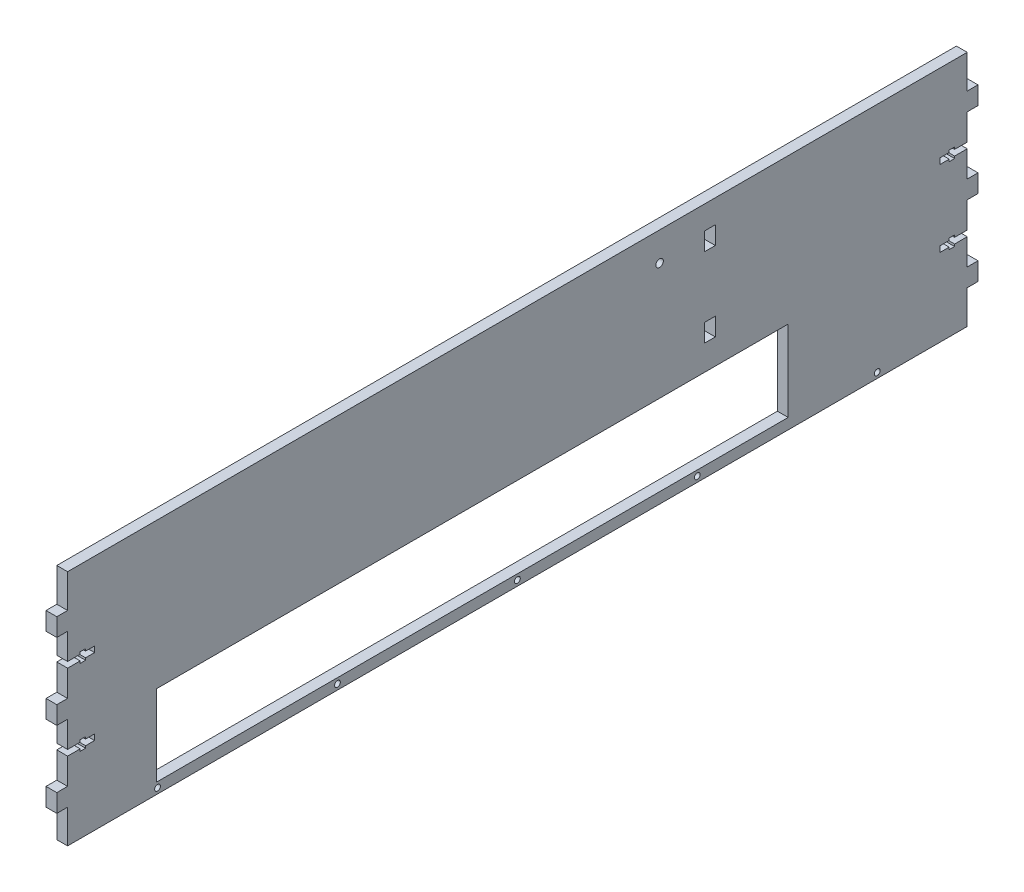
SolidWorks part; units mm, degrees
ref_plane "Front Plane" through (0, 0, 0) normal (0, 0, 1) x (1, 0, 0)
ref_plane "Top Plane" through (0, 0, 0) normal (0, 1, 0) x (1, 0, 0)
ref_plane "Right Plane" through (0, 0, 0) normal (1, 0, 0) x (0, 0, -1)
sketch "Sketch1" plane through (0, 0, 0) normal (1, 0, 0) x (0, 0, -1)
  line L1 (-250, -66) -> (250, -66)
  line L2 (-250, -66) -> (-250, 66)
  line L3 (-250, 66) -> (250, 66)
  line L4 (250, -66) -> (250, 66)
  line L5 (-250, -66) -> (250, 66) construction
  line L6 (-250, 66) -> (250, -66) construction
  point P0 (0, 0)
  dimension "D1" = 132
  dimension "D2" = 500
extrude "Boss-Extrude1" add sketch "Sketch1" along normal blind 6
sketch "Sketch4" plane through (0, 0, 250) normal (0, 0, 1) x (1, 0, 0)
  line L0 (0, 66) -> (0, -66) construction
  line L1 (0, 47.3321) -> (6, 47.3321)
  line L2 (0, 47.3321) -> (0, 37.3321)
  line L3 (0, 37.3321) -> (6, 37.3321)
  line L4 (6, 47.3321) -> (6, 37.3321)
  line L5 (6, 66) -> (6, -66) construction
  line L6 (0, 37.3321) -> (6, 37.3321) construction
  line L7 (0, -66) -> (0, 66) construction
  line L8 (6, 47.3321) -> (0, 47.3321) construction
  line L9 (0, -5) -> (6, -5) construction
  line L10 (0, -5) -> (6, -5)
  line L11 (0, -5) -> (0, 5)
  line L12 (0, 5) -> (6, 5)
  line L13 (6, -5) -> (6, 5)
  line L14 (6, -66) -> (6, 66) construction
  line L15 (6, 5) -> (0, 5) construction
  line L16 (6, -37.3321) -> (0, -37.3321) construction
  line L17 (0, -47.3321) -> (6, -47.3321)
  line L18 (0, -47.3321) -> (0, -37.3321)
  line L19 (0, -37.3321) -> (6, -37.3321)
  line L20 (6, -47.3321) -> (6, -37.3321)
  line L21 (0, -47.3321) -> (6, -47.3321) construction
extrude "Boss-Extrude2" add sketch "Sketch4" along normal blind 6
sketch "Sketch5" plane through (0, 0, 0) normal (-1, 0, 0) x (0, 0, 1)
  line L0 (250, 37.3321) -> (250, 5) construction
  line L1 (250, 5) -> (250, -5) construction
  line L2 (250, -5) -> (250, -37.3321) construction
  line L3 (250, 21.1661) -> (235, 21.1661) construction
  line L4 (240, -23.9661) -> (243, -18.3661) construction
  line L5 (250, 22.7661) -> (235, 22.7661)
  line L6 (240, -18.3661) -> (243, -23.9661) construction
  line L7 (250, 19.5661) -> (235, 19.5661)
  line L8 (250, -21.1661) -> (235, -21.1661) construction
  line L9 (250, 22.7661) -> (250, 19.5661)
  line L10 (235, 22.7661) -> (235, 19.5661)
  line L11 (243, -18.3661) -> (243, -23.9661)
  line L12 (240, -23.9661) -> (243, -23.9661)
  line L13 (250, 0) -> (222.8268, 0) construction
  line L14 (240, 18.3661) -> (243, 18.3661)
  line L15 (240, 18.3661) -> (240, 23.9661)
  line L16 (240, 23.9661) -> (243, 23.9661)
  line L17 (243, 18.3661) -> (243, 23.9661)
  line L18 (240, 18.3661) -> (243, 23.9661) construction
  line L19 (240, 23.9661) -> (243, 18.3661) construction
  line L20 (240, -18.3661) -> (240, -23.9661)
  line L21 (240, -18.3661) -> (243, -18.3661)
  line L22 (235, -22.7661) -> (235, -19.5661)
  line L23 (250, -22.7661) -> (250, -19.5661)
  line L24 (250, -19.5661) -> (235, -19.5661)
  line L25 (250, -22.7661) -> (235, -22.7661)
  point P20 (241.5, 21.1661)
  point P29 (241.5, -21.1661)
  dimension "D3" = 15
  dimension "D4" = 7
  dimension "D5" = 3
  dimension "D6" = 5.6
  dimension "D1" = 1.6
  dimension "D2" = 1.6
extrude "Cut-Extrude3" cut sketch "Sketch5" against normal up to next contours L17 L7 L9 L5 | L7 L17 L5 L15 | L5 L17 L16 L15 | L14 L17 L7 L15 | L7 L15 L5 L10 | L25 L23 L24 L11 | L25 L11 L24 L20 | L24 L11 L21 L20 | L11 L25 L20 L12 | L25 L20 L24 L22 region at (0, 21.1661, 246.5) region at (0, 21.1661, 241.5) region at (0, 23.3661, 241.5) region at (0, 21.1661, 237.5) region at (0, 18.9661, 241.5) region at (0, -18.9661, 241.5) region at (0, -21.1661, 246.5) region at (0, -21.1661, 241.5) region at (0, -23.3661, 241.5) region at (0, -21.1661, 237.5)
sketch "Sketch6" plane through (0, 0, -250) normal (0, 0, -1) x (-1, 0, 0)
  line L0 (0, 47.3321) -> (0, 37.3321) construction
  line L1 (0, 37.3321) -> (-6, 37.3321) construction
  line L2 (-6, 37.3321) -> (-6, 47.3321) construction
  line L3 (-6, 47.3321) -> (0, 47.3321) construction
  line L4 (0, 5) -> (0, -5) construction
  line L5 (0, -5) -> (-6, -5) construction
  line L6 (-6, -5) -> (-6, 5) construction
  line L7 (-6, 5) -> (0, 5) construction
  line L8 (0, -37.3321) -> (0, -47.3321) construction
  line L9 (0, -47.3321) -> (-6, -47.3321) construction
  line L10 (-6, -47.3321) -> (-6, -37.3321) construction
  line L11 (-6, -37.3321) -> (0, -37.3321) construction
  line L12 (0, 47.3321) -> (0, 37.3321)
  line L13 (0, 37.3321) -> (-6, 37.3321)
  line L14 (-6, 37.3321) -> (-6, 47.3321)
  line L15 (-6, 47.3321) -> (0, 47.3321)
  line L16 (0, 5) -> (0, -5)
  line L17 (0, -5) -> (-6, -5)
  line L18 (-6, -5) -> (-6, 5)
  line L19 (-6, 5) -> (0, 5)
  line L20 (0, -37.3321) -> (0, -47.3321)
  line L21 (0, -47.3321) -> (-6, -47.3321)
  line L22 (-6, -47.3321) -> (-6, -37.3321)
  line L23 (-6, -37.3321) -> (0, -37.3321)
extrude "Boss-Extrude3" add sketch "Sketch6" along normal blind 6
sketch "Sketch7" plane through (0, 0, 0) normal (-1, 0, 0) x (0, 0, 1)
  line L0 (0, 0) -> (0, -63.2146) construction
  line L1 (240, 22.7661) -> (240, 23.9661) construction
  line L2 (240, 22.7661) -> (235, 22.7661) construction
  line L3 (235, 22.7661) -> (235, 19.5661) construction
  line L4 (240, 19.5661) -> (235, 19.5661) construction
  line L5 (240, 18.3661) -> (240, 19.5661) construction
  line L6 (240, 18.3661) -> (243, 18.3661) construction
  line L7 (243, 18.3661) -> (243, 19.5661) construction
  line L8 (250, 19.5661) -> (243, 19.5661) construction
  line L9 (250, 22.7661) -> (243, 22.7661) construction
  line L10 (240, 23.9661) -> (243, 23.9661) construction
  line L11 (243, 22.7661) -> (243, 23.9661) construction
  line L12 (240, 22.7661) -> (235, 22.7661) construction
  line L13 (235, 22.7661) -> (235, 19.5661) construction
  line L14 (240, 19.5661) -> (235, 19.5661) construction
  line L15 (240, 18.3661) -> (240, 19.5661) construction
  line L16 (240, 18.3661) -> (243, 18.3661) construction
  line L17 (243, 18.3661) -> (243, 19.5661) construction
  line L18 (250, 19.5661) -> (243, 19.5661) construction
  line L19 (250, 22.7661) -> (243, 22.7661) construction
  line L20 (240, 23.9661) -> (243, 23.9661) construction
  line L21 (243, 22.7661) -> (243, 23.9661) construction
  line L22 (240, 22.7661) -> (240, 23.9661) construction
  line L23 (250, -19.5661) -> (243, -19.5661) construction
  line L24 (240, -18.3661) -> (243, -18.3661) construction
  line L25 (243, -18.3661) -> (243, -19.5661) construction
  line L26 (240, -18.3661) -> (240, -19.5661) construction
  line L27 (240, -19.5661) -> (235, -19.5661) construction
  line L28 (235, -22.7661) -> (235, -19.5661) construction
  line L29 (240, -22.7661) -> (235, -22.7661) construction
  line L30 (240, -22.7661) -> (240, -23.9661) construction
  line L31 (240, -23.9661) -> (243, -23.9661) construction
  line L32 (243, -22.7661) -> (243, -23.9661) construction
  line L33 (250, -22.7661) -> (243, -22.7661) construction
  line L34 (250, -19.5661) -> (243, -19.5661) construction
  line L35 (240, -18.3661) -> (243, -18.3661) construction
  line L36 (243, -18.3661) -> (243, -19.5661) construction
  line L37 (240, -18.3661) -> (240, -19.5661) construction
  line L38 (240, -19.5661) -> (235, -19.5661) construction
  line L39 (235, -22.7661) -> (235, -19.5661) construction
  line L40 (240, -22.7661) -> (235, -22.7661) construction
  line L41 (240, -22.7661) -> (240, -23.9661) construction
  line L42 (240, -23.9661) -> (243, -23.9661) construction
  line L43 (243, -22.7661) -> (243, -23.9661) construction
  line L44 (250, -22.7661) -> (243, -22.7661) construction
  line L45 (250, 22.7661) -> (250, 19.5661) construction
  line L46 (250, -19.5661) -> (250, -22.7661) construction
  line L47 (-250, -19.5661) -> (-250, -22.7661)
  line L48 (-250, 22.7661) -> (-250, 19.5661)
  line L49 (-250, -22.7661) -> (-243, -22.7661)
  line L50 (-243, -22.7661) -> (-243, -23.9661)
  line L51 (-240, -23.9661) -> (-243, -23.9661)
  line L52 (-240, -22.7661) -> (-240, -23.9661)
  line L53 (-240, -22.7661) -> (-235, -22.7661)
  line L54 (-235, -22.7661) -> (-235, -19.5661)
  line L55 (-240, -19.5661) -> (-235, -19.5661)
  line L56 (-240, -18.3661) -> (-240, -19.5661)
  line L57 (-243, -18.3661) -> (-243, -19.5661)
  line L58 (-240, -18.3661) -> (-243, -18.3661)
  line L59 (-250, -19.5661) -> (-243, -19.5661)
  line L60 (-240, 22.7661) -> (-240, 23.9661)
  line L61 (-243, 22.7661) -> (-243, 23.9661)
  line L62 (-240, 23.9661) -> (-243, 23.9661)
  line L63 (-250, 22.7661) -> (-243, 22.7661)
  line L64 (-250, 19.5661) -> (-243, 19.5661)
  line L65 (-243, 18.3661) -> (-243, 19.5661)
  line L66 (-240, 18.3661) -> (-243, 18.3661)
  line L67 (-240, 18.3661) -> (-240, 19.5661)
  line L68 (-240, 19.5661) -> (-235, 19.5661)
  line L69 (-235, 22.7661) -> (-235, 19.5661)
  line L70 (-240, 22.7661) -> (-235, 22.7661)
extrude "Cut-Extrude4" cut sketch "Sketch7" against normal up to next
sketch "Sketch8" plane through (0, 0, 0) normal (-1, 0, 0) x (0, 0, 1)
  line L0 (200, -15.55) -> (-150, -15.55) construction
  line L1 (200, -15.55) -> (-150, -15.55) construction
  line L2 (200, -15.55) -> (200, -60) construction
  line L3 (200, -15.55) -> (200, -60) construction
  line L186 (-150, -15.55) -> (-150, -60) construction
  line L187 (-150, -60) -> (200, -60) construction
  line L188 (200.5, -15.05) -> (200.5, -60)
  line L189 (200.5, -15.05) -> (-150.5, -15.05)
  line L190 (-150.5, -15.05) -> (-150.5, -60)
  line L191 (-150.5, -60) -> (200.5, -60)
  dimension "D1" = 0.5
extrude "Cut-Extrude5" cut sketch "Sketch8" against normal up to next
sketch "Sketch10" plane through (6, 0, 0) normal (1, 0, 0) x (0, 0, -1)
  line L0 (0, 0) -> (0, -66) construction
  line L1 (-250, -66) -> (250, -66) construction
  line L2 (0, -63) -> (250, -63) construction
  line L3 (250, -66) -> (250, -47.3321) construction
  circle A0 centre (0, -63) radius 1.6
  circle A1 centre (100, -63) radius 1.6
  circle A2 centre (200, -63) radius 1.6
  circle A3 centre (-100, -63) radius 1.6
  circle A4 centre (-200, -63) radius 1.6
  dimension "D2" = 3.2
  dimension "D1" = 3
  dimension "D3" = 100
  dimension "D4" = 100
extrude "Cut-Extrude7" cut sketch "Sketch10" against normal up to next
sketch "Sketch11" plane through (6, 0, 0) normal (1, 0, 0) x (0, 0, -1)
  line L0 (110, 43) -> (110, 53) construction
  line L1 (110, 53) -> (104, 53) construction
  line L2 (104, 53) -> (104, 43) construction
  line L3 (104, 43) -> (110, 43) construction
  line L4 (110, -1) -> (110, 9) construction
  line L5 (110, 9) -> (104, 9) construction
  line L6 (104, 9) -> (104, -1) construction
  line L7 (104, -1) -> (110, -1) construction
  line L8 (110, 43) -> (110, 53)
  line L9 (110, 53) -> (104, 53)
  line L10 (104, 53) -> (104, 43)
  line L11 (104, 43) -> (110, 43)
  line L12 (110, -1) -> (110, 9)
  line L13 (110, 9) -> (104, 9)
  line L14 (104, 9) -> (104, -1)
  line L15 (104, -1) -> (110, -1)
extrude "Cut-Extrude8" cut sketch "Sketch11" against normal up to next
sketch "Sketch12" plane through (0, 0, 0) normal (-1, 0, 0) x (0, 0, 1)
  line L0 (-104, 53) -> (-104, 43) construction
  line L1 (-250, 66) -> (250, 66) construction
  circle A0 centre (-79, 50) radius 2.1
  dimension "D1" = 25
  dimension "D3" = 4.2
  dimension "D2" = 16
extrude "Cut-Extrude9" cut sketch "Sketch12" against normal up to next
